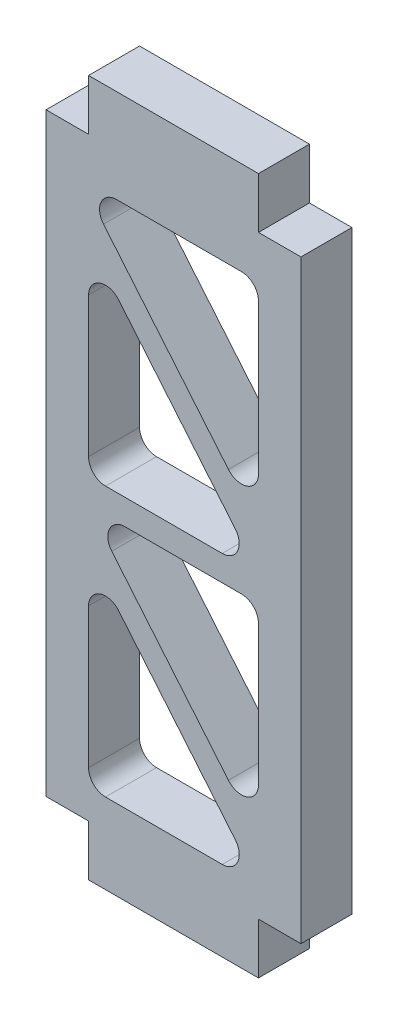
SolidWorks part; units mm, degrees
material "Acrílico (Impacto medio-alto)"
ref_plane "Alzado" through (0, 0, 0) normal (0, 0, 1) x (1, 0, 0)
ref_plane "Planta" through (0, 0, 0) normal (0, 1, 0) x (1, 0, 0)
ref_plane "Vista lateral" through (0, 0, 0) normal (1, 0, 0) x (0, 0, -1)
sketch "Croquis1" plane through (0, 0, 0) normal (0, 0, 1) x (1, 0, 0)
  line L0 (0, 0) -> (0, 14.9643) construction
  line L1 (7.5, -20.5) -> (-7.5, -20.5)
  line L2 (7.5, -20.5) -> (7.5, 20.5)
  line L3 (7.5, 20.5) -> (-7.5, 20.5)
  line L4 (-7.5, -20.5) -> (-7.5, 20.5)
  line L5 (7.5, -20.5) -> (-7.5, 20.5) construction
  line L6 (7.5, 20.5) -> (-7.5, -20.5) construction
  line L7 (0, 0) -> (-16.1003, 0) construction
  line L8 (-5, -23.5) -> (-10, -23.5)
  line L9 (-5, 17.5) -> (-10, 17.5)
  line L10 (-5, 17.5) -> (-5, 23.5)
  line L11 (-5, 23.5) -> (-10, 23.5)
  line L12 (-10, 17.5) -> (-10, 23.5)
  line L13 (-5, 17.5) -> (-10, 23.5) construction
  line L14 (-5, 23.5) -> (-10, 17.5) construction
  line L15 (-10, -17.5) -> (-10, -23.5)
  line L16 (-5, -17.5) -> (-10, -17.5)
  line L17 (-5, -17.5) -> (-5, -23.5)
  line L18 (5, -17.5) -> (5, -23.5)
  line L19 (5, -17.5) -> (10, -17.5)
  line L20 (10, -17.5) -> (10, -23.5)
  line L21 (5, -23.5) -> (10, -23.5)
  line L22 (5, 23.5) -> (10, 23.5)
  line L23 (10, 17.5) -> (10, 23.5)
  line L24 (5, 17.5) -> (10, 17.5)
  line L25 (5, 17.5) -> (5, 23.5)
  line L26 (-4.121, 13.3598) -> (3.2318, 4.5365)
  line L27 (5, 5.1767) -> (5, 14)
  line L28 (4, 15) -> (-3.3528, 15)
  line L29 (-3.2318, 9.9497) -> (3.6332, 1.7117)
  line L30 (2.865, 0.0716) -> (-4, 0.0716)
  line L31 (-5, 1.0716) -> (-5, 9.3095)
  line L32 (-2.865, -1.4284) -> (4, -1.4284)
  line L33 (5, -2.4284) -> (5, -10.6664)
  line L34 (3.2318, -11.3066) -> (-3.6332, -3.0686)
  line L35 (-3.2318, -5.8934) -> (3.638, -14.1372)
  line L36 (2.8698, -15.7773) -> (-4, -15.7773)
  line L37 (-5, -14.7773) -> (-5, -6.5336)
  arc A0 (-4.121, 13.3598) -> (-3.3528, 15) centre (-3.3528, 14) cw
  arc A1 (3.2318, 4.5365) -> (5, 5.1767) centre (4, 5.1767) ccw
  arc A2 (5, 14) -> (4, 15) centre (4, 14) ccw
  arc A3 (-3.2318, 9.9497) -> (-5, 9.3095) centre (-4, 9.3095) ccw
  arc A4 (-4, 0.0716) -> (-5, 1.0716) centre (-4, 1.0716) cw
  arc A5 (3.6332, 1.7117) -> (2.865, 0.0716) centre (2.865, 1.0716) cw
  arc A6 (4, -1.4284) -> (5, -2.4284) centre (4, -2.4284) cw
  arc A7 (5, -10.6664) -> (3.2318, -11.3066) centre (4, -10.6664) cw
  arc A8 (-2.865, -1.4284) -> (-3.6332, -3.0686) centre (-2.865, -2.4284) ccw
  arc A9 (-3.2318, -5.8934) -> (-5, -6.5336) centre (-4, -6.5336) ccw
  arc A10 (3.638, -14.1372) -> (2.8698, -15.7773) centre (2.8698, -14.7773) cw
  arc A11 (-4, -15.7773) -> (-5, -14.7773) centre (-4, -14.7773) cw
  point P0 (0, 0)
  point P36 (0, 0)
  point P38 (0, 0)
  point P39 (0, 0)
  point P40 (0, 0)
  point P43 (-5.4878, 15)
  point P46 (5, 2.4146)
  point P49 (5, 14.4146)
  point P52 (-5, 12.0716)
  point P55 (-5, 0.0716)
  point P58 (5, 0.0716)
  point P61 (5, -1.4284)
  point P64 (5, -13.4284)
  point P67 (-5, -1.4284)
  point P70 (-5, -3.7715)
  point P75 (-5.1411, -15.7707)
  point P76 (0, 0)
  point P77 (0, 0)
  point P78 (0, 0)
  dimension "D12" = 1
  dimension "D15" = 2.5
  dimension "D1" = 6
  dimension "D2" = 15
  dimension "D3" = 41
  dimension "D4" = 5
  dimension "D5" = 12
  dimension "D6" = 12
  dimension "D7" = 12
  dimension "D8" = 12
  dimension "D9" = 1.5
  dimension "D10" = 1.5
  dimension "D11" = 1.5
  dimension "D13" = 5.5
  dimension "D14" = 2.5
extrude "Saliente-Extruir1" add sketch "Croquis1" along normal blind 3 contours L24 L25 L3 L10 L9 L4 L16 L17 L1 L18 L19 L2 region at (0, -20.0634, 0)
